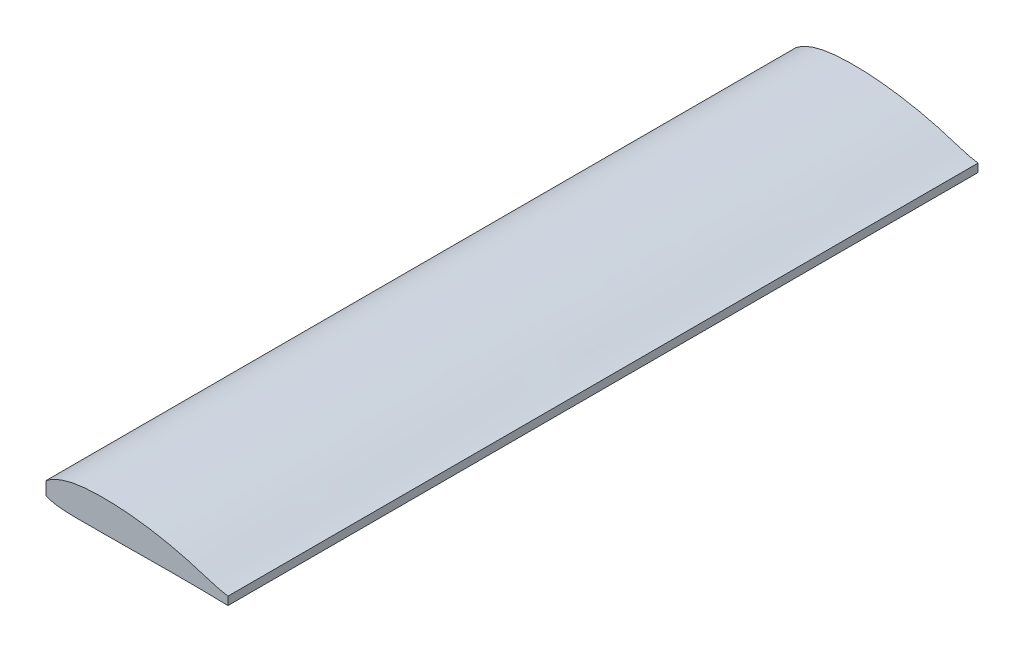
SolidWorks part; units mm, degrees
ref_plane "Alzado" through (0, 0, 0) normal (0, 0, 1) x (1, 0, 0)
ref_plane "Planta" through (0, 0, 0) normal (0, 1, 0) x (1, 0, 0)
ref_plane "Vista lateral" through (0, 0, 0) normal (1, 0, 0) x (0, 0, -1)
sketch "Croquis1" plane through (0, 0, 0) normal (0, 0, 1) x (1, 0, 0)
  line L0 (-36.2317, 4.0515) -> (109.4255, 4.0515) construction
  line L1 (0, 0) -> (0, 52520.6258) construction
  line L2 (0, 0) -> (52520.6258, 0) construction
  line L3 (-63.4541, -9.256) -> (-63.4541, 3.9563)
  line L4 (156.5459, -5.5922) -> (156.5459, -15.4449)
  spline S0 degree 3 poles (-63.4541, 3.9563) (-47.4948, 17.3868) (12.4625, 27.2232) (97.0433, 13.2049) (145.1549, -4.0867) (156.5459, -5.5922) knots 0 0 0 0 0.319357 0.833459 1 1 1 1
  spline S1 degree 3 poles (156.5459, -15.4449) (100.614, -13.7876) (10.6003, -16.0387) (-54.0351, -15.0655) (-63.4541, -9.256) knots 0 0 0 0 0.768101 1 1 1 1
  dimension "D1" = 220
extrude "CuerpoPrincipal" add sketch "Croquis1" along normal blind 450 and the other way blind 450
ref_plane "Plano1" through (0, 30, 0) normal (0, 1, 0) x (1, 0, 0)
sketch "Croquis3" plane through (0, 30, 0) normal (0, 1, 0) x (1, 0, 0)
  line L0 (39.9202, -517.5222) -> (39.9202, 529.1445) construction
  line L1 (0, 0) -> (50000, 0) construction
  line L2 (0, 0) -> (0, 50000) construction
  line L3 (-61.8161, -677.9811) -> (-61.8161, 689.4197)
  line L4 (160.478, 633.3888) -> (160.478, -602.9677)
  line L5 (-63.4541, 450) -> (156.5459, 450)
  line L6 (156.5459, 450) -> (156.5459, -450)
  line L7 (156.5459, -450) -> (-63.4541, -450)
  line L8 (-63.4541, -450) -> (-63.4541, 450)
  spline S0 degree 3 poles (-61.8161, 689.4197) (-55.9672, 757.9487) (-8.7613, 811.2886) (128.3678, 760.8254) (158.5772, 680.16) (160.478, 633.3888) knots 0 0 0 0 0.335371 0.617626 1 1 1 1
  spline S1 degree 3 poles (-61.8161, -677.9811) (-59.4256, -725.131) (-41.9994, -786.3822) (37.4073, -799.4062) (102.12, -770.9569) (153.3654, -697.7577) (163.3055, -642.2795) (160.478, -602.9677) knots 0 0 0 0 0.28667 0.347599 0.609293 0.716869 1 1 1 1
  dimension "D1" = 6.352
  dimension "D2" = 39.9202
  dimension "D3" = 103.6494
  dimension "D4" = 111.9734
  dimension "D5" = 140.2368
  dimension "D6" = 147.5624
  dimension "D7" = 160.478
  dimension "D8" = 61.8161
  dimension "D9" = 633.3888
  dimension "D10" = 689.4197
  dimension "D11" = 696.2446
  dimension "D12" = 757.3784
  dimension "D13" = 790.959
  dimension "D14" = 602.9677
  dimension "D15" = 677.9811
  dimension "D16" = 712.2229
  dimension "D17" = 752.2211
  dimension "D18" = 792.9265
extrude "Redondeo" cut sketch "Croquis3" against normal through all contours S1 L3 S0 L6 L5 L8 L7 region at (-62.6351, 30, 0)
